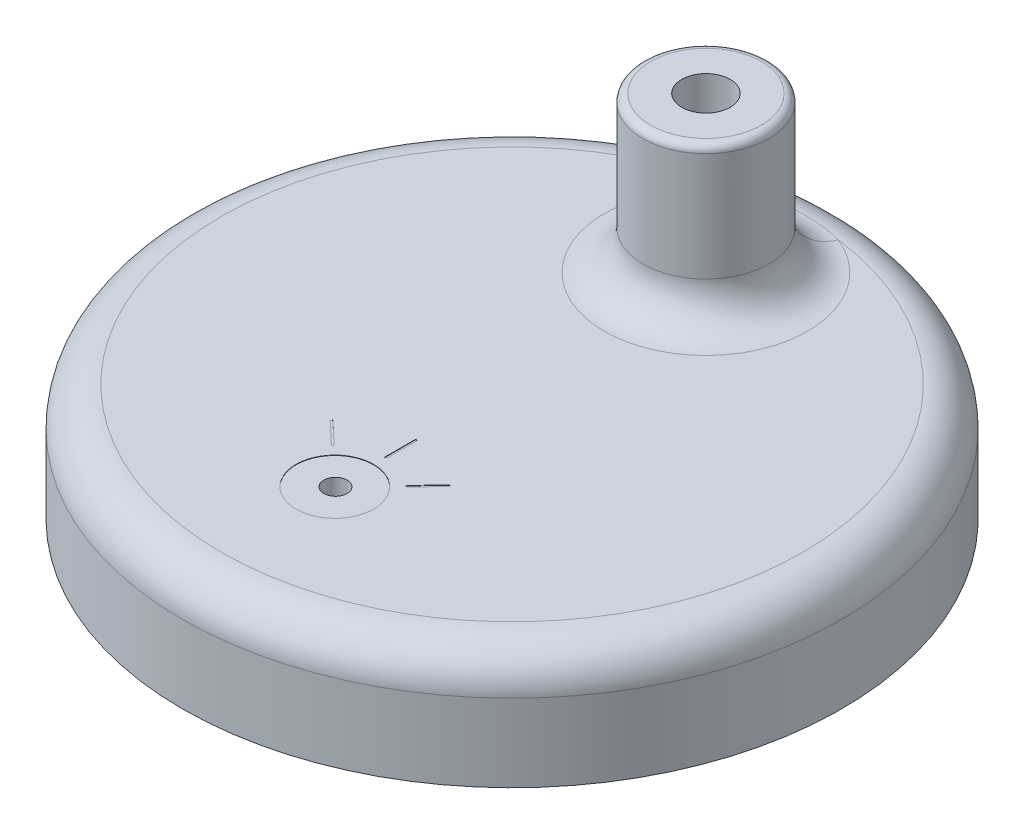
SolidWorks part; units mm, degrees
ref_plane "Front Plane" through (0, 0, 0) normal (0, 0, 1) x (1, 0, 0)
ref_plane "Top Plane" through (0, 0, 0) normal (0, 1, 0) x (1, 0, 0)
ref_plane "Right Plane" through (0, 0, 0) normal (1, 0, 0) x (0, 0, -1)
sketch "Sketch1" plane through (0, 0, 0) normal (0, 1, 0) x (1, 0, 0)
  circle A0 centre (0, 0) radius 85
  dimension "D1" = 170
extrude "Boss-Extrude1" add sketch "Sketch1" along normal blind 30
fillet "Fillet1" radius 10 1 edges at (0, 30, 85)
shell "Shell1" thickness 8 removed face at (0, 0, 85)
extrude "Boss-Extrude3" add sketch "Sketch1<2>" along normal blind 5
sketch "Sketch1<2>" plane through (0, 0, 0) normal (0, 1, 0) x (1, 0, 0) same geometry as "Sketch1"
sketch "Sketch2" plane through (0, 30, 0) normal (0, 1, 0) x (1, 0, 0)
  line L0 (0, 0) -> (0, 50) construction
  circle A0 centre (0, 50) radius 6.25
  circle A1 centre (0, 50) radius 16.25
  dimension "D1" = 50
  dimension "D2" = 12.5
  dimension "D3" = 10
extrude "Boss-Extrude2" add sketch "Sketch2" along normal blind 40
extrude "Cut-Extrude1" cut sketch "Sketch2<3>" against normal up to next contours A0 region at (0, 30, -50)
sketch "Sketch2<3>" plane through (0, 30, 0) normal (0, 1, 0) x (1, 0, 0) same geometry as "Sketch2"
fillet "Fillet2" radius 10 1 edges at (0, 30, -33.75)
fillet "Fillet3" radius 2 1 edges at (0, 70, -33.75)
sketch "Sketch3" plane through (0, 30, 0) normal (0, 1, 0) x (1, 0, 0)
  circle A0 centre (0, -45.5544) radius 3
extrude "Cut-Extrude2" cut sketch "Sketch3" against normal blind 5
sketch "Sketch4" plane through (0, 30, 0) normal (0, 1, 0) x (1, 0, 0)
  line L0 (0, -45.7185) -> (0, -28.3379) construction
  line L9 (0, -45.7185) -> (20.1282, -45.7185) construction
  line L10 (0, -45.7185) -> (-22.7242, -45.7185) construction
  line L11 (0, -45.7185) -> (-18.0086, -28.7122) construction
  line L12 (0, -45.7185) -> (16.7313, -28.0011) construction
  line L13 (8.9292, -36.2702) -> (9.2927, -36.6135)
  line L18 (-0.1699, -32.7185) -> (0.3301, -32.7185)
  line L19 (0.3301, -32.7185) -> (0.3301, -24.7185)
  line L28 (9.2927, -36.6135) -> (14.7854, -30.7971)
  line L29 (14.7854, -30.7971) -> (14.4219, -30.4538)
  line L30 (14.4219, -30.4538) -> (8.9292, -36.2702)
  line L31 (-9.28, -36.6111) -> (-9.6233, -36.9746)
  line L32 (-9.6233, -36.9746) -> (-15.4397, -31.482)
  line L33 (-15.4397, -31.482) -> (-15.0964, -31.1184)
  line L34 (-15.0964, -31.1184) -> (-9.28, -36.6111)
  line L35 (0.3301, -24.7185) -> (-0.1699, -24.7185)
  line L36 (-0.1699, -24.7185) -> (-0.1699, -32.7185)
  circle A0 centre (0, -45.7185) radius 10
  point P5 (0, -29.9847)
  point P11 (0, 0)
  dimension "D1" = 13
  dimension "D2" = 13
  dimension "D3" = 13
  dimension "D4" = 8
  dimension "D5" = 8
  dimension "D6" = 8
  dimension "D7" = 0.5
  dimension "D8" = 0.5
  dimension "D9" = 0.5
  dimension "D10" = 0.505
  dimension "D11" = 0.3301
  dimension "D12" = 0.25
extrude "Cut-Extrude3" cut sketch "Sketch4" against normal blind 0.1
